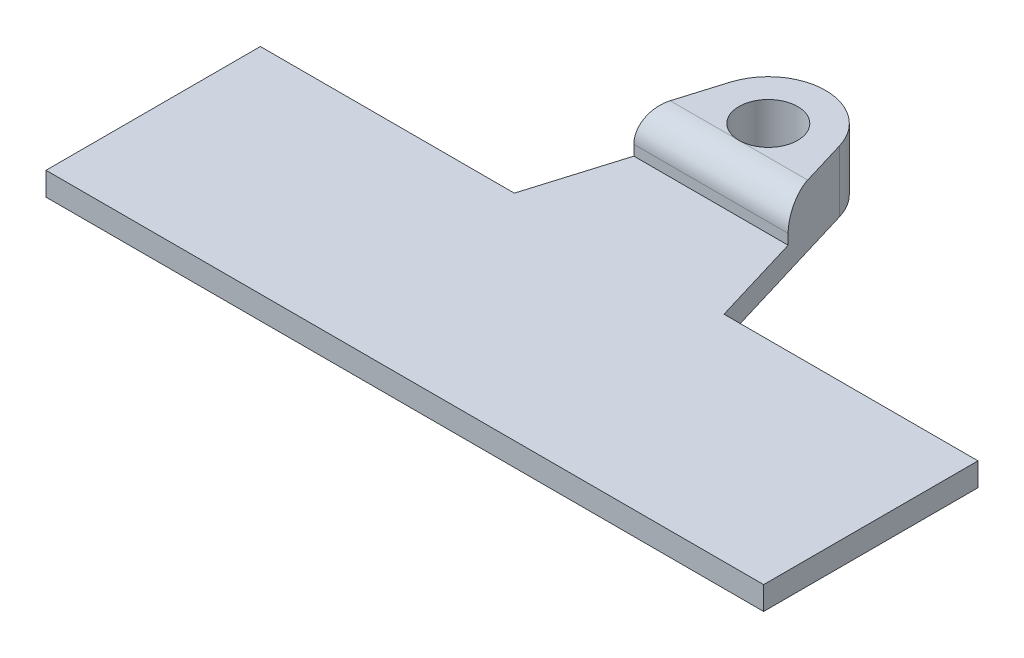
SolidWorks part; units mm, degrees
ref_plane "前视基准面" through (0, 0, 0) normal (0, 0, 1) x (1, 0, 0)
ref_plane "上视基准面" through (0, 0, 0) normal (0, 1, 0) x (1, 0, 0)
ref_plane "右视基准面" through (0, 0, 0) normal (1, 0, 0) x (0, 0, -1)
sketch "草图1" plane through (0, 0, 0) normal (0, 1, 0) x (1, 0, 0)
  line L0 (-11.2496, 0) -> (-5.888, 17.7759)
  line L1 (-38.5, 0) -> (38.5, 0)
  line L2 (-38.5, 0) -> (-38.5, -23)
  line L3 (-38.5, -23) -> (38.5, -23)
  line L4 (38.5, 0) -> (38.5, -23)
  line L5 (5.888, 17.7759) -> (11.2496, 0)
  circle A0 centre (0, 16) radius 3.15
  arc A1 (-5.888, 17.7759) -> (5.888, 17.7759) centre (0, 16) cw
  point P4 (0, 0)
  point P12 (0, 0)
  dimension "D3" = 6.3
  dimension "D5" = 3
  dimension "D1" = 77
  dimension "D2" = 23
  dimension "D4" = 16
extrude "凸台-拉伸1" add sketch "草图1" along normal blind 6.6 contours A1 L0 L1 L5 A0 | L4 L1 L2 L3 region at (0, 0, 11.5) region at (0, 0, -8.5712)
sketch "草图2" plane through (0, 0, 0) normal (1, 0, 0) x (0, 0, -1)
  line L0 (-23, 2.5) -> (9.85, 2.5)
  line L1 (-23, 6.6) -> (-23, 0) construction
  line L2 (9.85, 2.5) -> (9.85, 6.6)
  line L3 (17.7759, 6.6) -> (0, 6.6) construction
  line L4 (19.15, 6.6) -> (12.85, 6.6) construction
  line L5 (19.15, 6.6) -> (12.85, 6.6) construction
  line L6 (0, 0) -> (-23, 0) construction
  point P11 (0, 0)
  dimension "D1" = 2.5
  dimension "D2" = 3
extrude "切除-拉伸1" cut sketch "草图2" against normal through all both and the other way through all
fillet "圆角1" radius 3 1 edges at (0, 6.6, -9.85)
